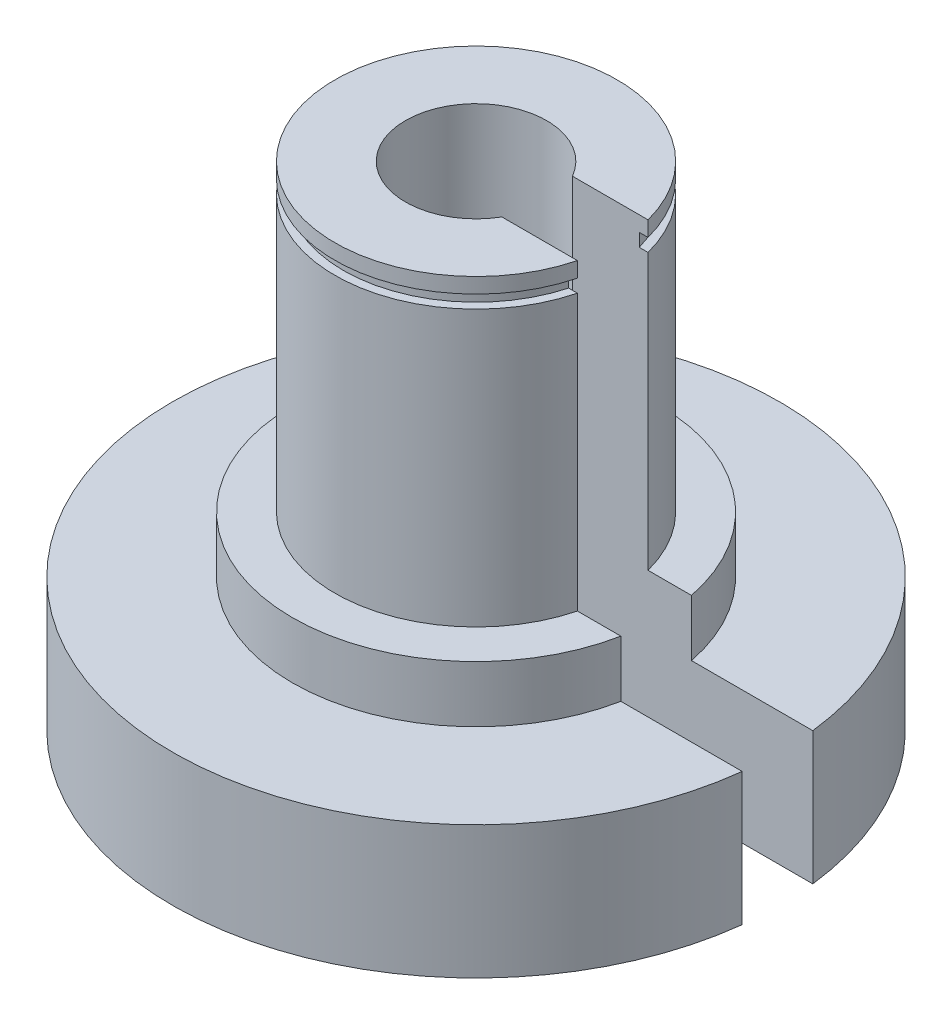
SolidWorks part; units mm, degrees
material "6061-T6 (SS)"
ref_plane "Front Plane" through (0, 0, 0) normal (0, 0, 1) x (1, 0, 0)
ref_plane "Top Plane" through (0, 0, 0) normal (0, 1, 0) x (1, 0, 0)
ref_plane "Right Plane" through (0, 0, 0) normal (1, 0, 0) x (0, 0, -1)
sketch "Sketch1" plane through (0, 0, 0) normal (0, 1, 0) x (1, 0, 0)
  circle A0 centre (0, 0) radius 27.305
  circle A1 centre (0, 0) radius 4.5466
  dimension "D1" = 54.61
  dimension "D2" = 9.0932
extrude "Boss-Extrude1" add sketch "Sketch1" along normal blind 57.658
sketch "Sketch2" plane through (0, 57.658, 0) normal (0, 1, 0) x (1, 0, 0)
  circle A0 centre (0, 0) radius 6.35
  dimension "D1" = 12.7
extrude "Cut-Extrude1" cut sketch "Sketch2" against normal blind 44.45
sketch "Sketch3" plane through (0, 57.658, 0) normal (0, 1, 0) x (1, 0, 0)
  circle A0 centre (0, 0) radius 12.7
  dimension "D1" = 25.4
extrude "Cut-Extrude2" cut sketch "Sketch3" against normal blind 44.45 flip side to cut
ref_plane "Plane6" through (0, 44.323, 0) normal (0, 1, 0) x (-1, 0, 0)
ref_plane "Plane1" through (0, 24.3205, 0) normal (0, 1, 0) x (-1, 0, 0)
sketch "Sketch10" plane through (0, 0, 0) normal (0, -1, 0) x (1, 0, 0)
  line L1 (2.4998, -3.175) -> (33.1793, -3.175)
  line L2 (2.4998, -3.175) -> (2.4998, 3.175)
  line L3 (2.4998, 3.175) -> (33.1793, 3.175)
  line L4 (33.1793, -3.175) -> (33.1793, 3.175)
  dimension "D1" = 6.35
  dimension "D2" = 3.175
extrude "Cut-Extrude7" cut sketch "Sketch10" against normal blind 6.35
ref_plane "Plane4" through (0, 41.783, 0) normal (0, 1, 0) x (-1, 0, 0)
sketch "Sketch13" plane through (0, 41.783, 0) normal (0, 1, 0) x (-1, 0, 0)
  circle A3 centre (0, 0) radius 11.938
  dimension "D1" = 23.876
extrude "Cut-Extrude9" cut sketch "Sketch13" along normal blind 1.1684 flip side to cut
ref_plane "Plane5" through (0, 30.6705, 0) normal (0, 1, 0) x (-1, 0, 0)
sketch "Sketch16" plane through (0, 44.323, 0) normal (0, 1, 0) x (-1, 0, 0)
  circle A0 centre (0, 0) radius 46.0824
extrude "Cut-Extrude11" cut sketch "Sketch16" along normal through all
sketch "Sketch18" plane through (0, 13.208, 0) normal (0, 1, 0) x (1, 0, 0)
  circle A2 centre (0, 0) radius 16.51
  circle A3 centre (0, 0) radius 12.7
  circle A4 centre (0, 0) radius 12.7
  dimension "D1" = 0
  dimension "D2" = 3.81
extrude "Boss-Extrude4" add sketch "Sketch18" along normal blind 3.81
sketch "Sketch19" plane through (0, 13.208, 0) normal (0, 1, 0) x (1, 0, 0)
  circle A2 centre (0, 0) radius 16.51
  circle A3 centre (0, 0) radius 16.51
  dimension "D1" = 0
extrude "Cut-Extrude12" cut sketch "Sketch19" against normal blind 1.27 flip side to cut
extrude "Cut-Extrude13" cut sketch "Sketch10<2>" against normal through all
sketch "Sketch10<2>" plane through (0, 0, 0) normal (0, -1, 0) x (1, 0, 0) same geometry as "Sketch10"
